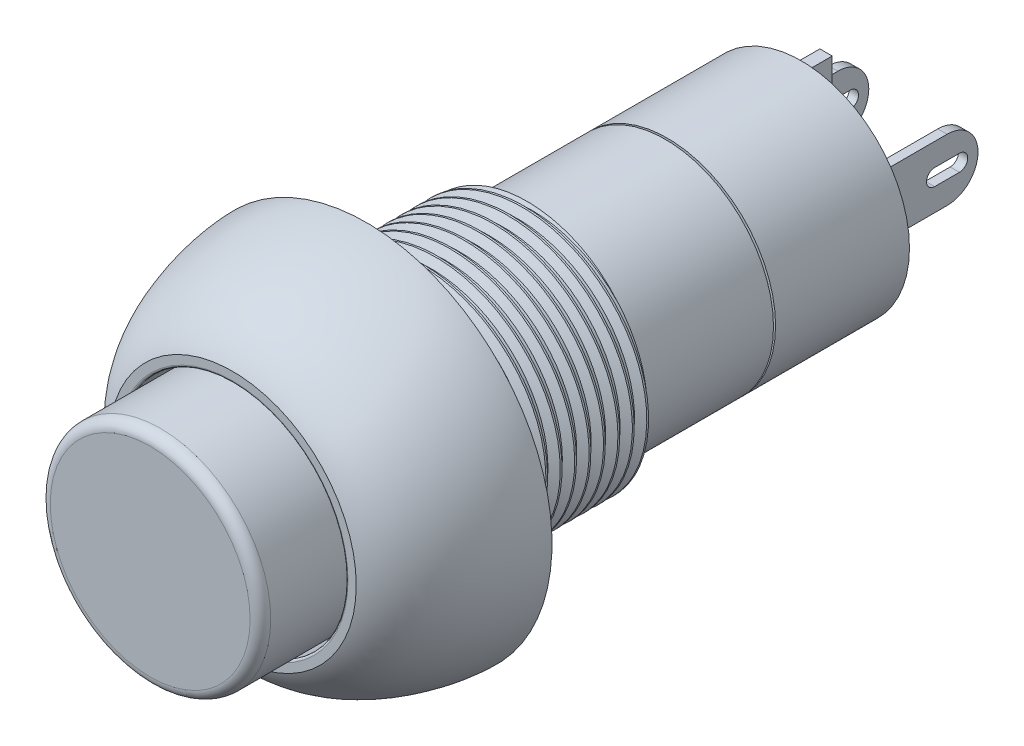
SolidWorks part; units mm, degrees
ref_plane "Спереди" through (0, 0, 0) normal (0, 0, 1) x (1, 0, 0)
ref_plane "Сверху" through (0, 0, 0) normal (0, 1, 0) x (1, 0, 0)
ref_plane "Справа" through (0, 0, 0) normal (1, 0, 0) x (0, 0, -1)
sketch "Эскиз1" plane through (0, 0, 0) normal (0, 0, 1) x (1, 0, 0)
  circle A0 centre (0, 0) radius 6
  dimension "D1" = 12
extrude "Бобышка-Вытянуть1" add sketch "Эскиз1" along normal blind 8
sketch "Эскиз2" plane through (0, 0, 0) normal (0, 0, -1) x (-1, 0, 0)
  circle A0 centre (0, 0) radius 5.25
  dimension "D1" = 10.5
extrude "Бобышка-Вытянуть2" add sketch "Эскиз2" along normal blind 6.5
thread "Резьба1" pitch 0.7 method cut profile "Профиль резьбы1" start angle 0, offset 1, length 10, pitch 0.7, diameter 12
ref_plane "Плоскость4" through (6, 0, -1) normal (0, -1, 0) x (1, 0, 0)
sketch "Профиль резьбы1" plane through (6, 0, -1) normal (0, -1, 0) x (1, 0, 0)
  line L0 (0, 0) -> (0, 0.7) construction
  line L11 (0, 0) -> (0, 0.6125)
  line L12 (0, 0.6125) -> (-0.3789, 0.3937)
  line L13 (-0.3789, 0.3937) -> (-0.3789, 0.2187)
  line L15 (-0.3789, 0.2187) -> (0, 0)
  line L17 (-0.3789, 0.3062) -> (0, 0.3062) construction
  point P2 (0, 0)
  dimension "Pitch" = 0.7
  dimension "Profile_Angle" = 60
  dimension "Profile_Land" = 0.175
  dimension "Profile_Height" = 0.3789
sketch "Эскиз8" plane through (0, 0, -6.5) normal (0, 0, -1) x (-1, 0, 0)
  circle A0 centre (0, 0) radius 5.1
  dimension "D1" = 10.2
extrude "Бобышка-Вытянуть3" add sketch "Эскиз8" along normal blind 0.1
sketch "Эскиз9" plane through (0, 0, -6.6) normal (0, 0, -1) x (-1, 0, 0)
  circle A0 centre (0, 0) radius 5.25 construction
  circle A1 centre (0, 0) radius 5.25
extrude "Бобышка-Вытянуть4" add sketch "Эскиз9" along normal blind 6.5
sketch "Эскиз10" plane through (0, 0, -13.1) normal (0, 0, -1) x (-1, 0, 0)
  circle A0 centre (0, 0) radius 5.25 construction
  circle A1 centre (0, 0) radius 5.25 construction
  circle A2 centre (0, 0) radius 5
  dimension "D1" = 0.25
extrude "Вырез-Вытянуть1" cut sketch "Эскиз10" against normal blind 0.3
sketch "Эскиз11" plane through (0, 0, -12.8) normal (0, 0, -1) x (-1, 0, 0)
  line L0 (0, 5) -> (0, -5) construction
  line L1 (-0.3, 5) -> (-0.3, -5)
  line L2 (0.3, 5) -> (0.3, -5)
  line L3 (-0.3, 5) -> (0.3, 5)
  line L4 (-0.3, -5) -> (0.3, -5)
  circle A0 centre (0, 0) radius 5 construction
  circle A1 centre (0, 0) radius 5 construction
  dimension "D1" = 0.3
  dimension "D2" = 0.3
extrude "Бобышка-Вытянуть5" add sketch "Эскиз11" along normal blind 1.5
sketch "Эскиз12" plane through (0, 0, -12.8) normal (0, 0, -1) x (-1, 0, 0)
  line L0 (-0.3, 0) -> (-5, 0) construction
  line L1 (-0.3, 5) -> (-0.3, -5) construction
  line L2 (-2.9, -2.5) -> (-2.4, -2.5)
  line L3 (-2.9, -2.5) -> (-2.9, -0.433)
  line L4 (-2.4, -2.5) -> (-2.4, -0.433)
  line L5 (-2.9, 2.5) -> (-2.4, 2.5)
  line L6 (0, 5) -> (0, -5) construction
  line L7 (-0.3, 5) -> (0.3, 5) construction
  line L8 (-2.4, 0.433) -> (-2.4, 2.5)
  line L9 (-2.9, 0.433) -> (-2.9, 2.5)
  line L10 (-0.3, -5) -> (0.3, -5) construction
  line L11 (2.9, 0.433) -> (2.9, 2.5)
  line L12 (2.9, -2.5) -> (2.9, -0.433)
  line L13 (2.9, -2.5) -> (2.4, -2.5)
  line L14 (2.4, -2.5) -> (2.4, -0.433)
  line L15 (2.4, 0.433) -> (2.4, 2.5)
  line L16 (2.9, 2.5) -> (2.4, 2.5)
  arc A0 (-0.3, 4.991) -> (-0.3, -4.991) centre (0, 0) ccw construction
  arc A1 (-2.4, -0.433) -> (-2.4, 0.433) centre (-2.65, 0) ccw
  arc A2 (-2.9, 0.433) -> (-2.9, -0.433) centre (-2.65, 0) ccw
  arc A3 (2.9, 0.433) -> (2.9, -0.433) centre (2.65, 0) cw
  arc A4 (2.4, -0.433) -> (2.4, 0.433) centre (2.65, 0) cw
  dimension "D1" = 1
  dimension "D2" = 0.5
  dimension "D3" = 5
  dimension "D4" = 0.25
  dimension "D5" = 2.5
extrude "Вырез-Вытянуть2" cut sketch "Эскиз12" against normal blind 4
sketch "Эскиз13" plane through (0, 0, -8.8) normal (0, 0, -1) x (-1, 0, 0)
  line L0 (-3.15, 0) -> (-2.15, 0) construction
  line L1 (-2.875, -2.475) -> (-2.425, -2.475)
  line L2 (-2.875, -2.475) -> (-2.875, 2.475)
  line L3 (-2.425, -2.475) -> (-2.425, 2.475)
  line L4 (-2.875, 2.475) -> (-2.425, 2.475)
  line L5 (-2.875, -2.475) -> (-2.425, 2.475) construction
  line L6 (-2.425, -2.475) -> (-2.875, 2.475) construction
  line L7 (0, 0) -> (0, 5) construction
  line L8 (-0.3, 5) -> (0.3, 5) construction
  line L9 (2.425, -2.475) -> (2.425, 2.475)
  line L10 (2.875, 2.475) -> (2.425, 2.475)
  line L11 (2.875, -2.475) -> (2.875, 2.475)
  line L12 (2.875, -2.475) -> (2.425, -2.475)
  arc A0 (-2.9, 0.433) -> (-2.9, -0.433) centre (-2.65, 0) ccw construction
  arc A1 (-2.4, -0.433) -> (-2.4, 0.433) centre (-2.65, 0) ccw construction
  point P9 (-2.65, 0)
  dimension "D1" = 4.95
  dimension "D2" = 0.45
extrude "Бобышка-Вытянуть6" add sketch "Эскиз13" along normal blind 4.5
sketch "Эскиз14" plane through (0, 0, -13.3) normal (0, 0, -1) x (-1, 0, 0)
  line L0 (-2.65, 2.475) -> (-2.65, -2.475) construction
  line L1 (-2.425, 2.475) -> (-2.875, 2.475) construction
  line L2 (-2.875, -2.475) -> (-2.425, -2.475) construction
  line L3 (-2.875, -1.5) -> (-2.425, -1.5)
  line L4 (-2.875, -1.5) -> (-2.875, 1.5)
  line L5 (-2.425, -1.5) -> (-2.425, 1.5)
  line L6 (-2.875, 1.5) -> (-2.425, 1.5)
  line L7 (-2.875, -1.5) -> (-2.425, 1.5) construction
  line L8 (-2.425, -1.5) -> (-2.875, 1.5) construction
  line L9 (-2.875, 2.475) -> (-2.875, -2.475) construction
  line L10 (0, 0) -> (0, 5) construction
  line L11 (-0.3, 5) -> (0.3, 5) construction
  line L12 (2.425, -1.5) -> (2.425, 1.5)
  line L13 (2.875, 1.5) -> (2.425, 1.5)
  line L14 (2.875, -1.5) -> (2.875, 1.5)
  line L15 (2.875, -1.5) -> (2.425, -1.5)
  point P7 (-2.65, 0)
  dimension "D1" = 3
extrude "Бобышка-Вытянуть7" add sketch "Эскиз14" along normal blind 5.5
sketch "Эскиз15" plane through (2.875, 0, 0) normal (1, 0, 0) x (0, 0, -1)
  line L0 (18.8, 0) -> (13.1, 0) construction
  line L1 (18.8, 1.5) -> (18.8, -1.5) construction
  line L2 (13.1, -5.25) -> (13.1, 5.25) construction
  line L3 (18.8, 1.5) -> (13.3, 1.5) construction
  line L4 (16.7, 0) -> (17.9, 0) construction
  line L7 (17.3, 1.5) -> (17.3, 1.8711)
  line L8 (17.3, 1.8711) -> (19.8995, 1.8711)
  line L9 (19.8995, 1.8711) -> (19.8995, -2.2852)
  line L10 (19.8995, -2.2852) -> (17.3, -2.2852)
  line L11 (17.3, -2.2852) -> (17.3, -1.5)
  line L12 (18.8, -1.5) -> (13.3, -1.5) construction
  line L13 (16.7, 0.4) -> (17.9, 0.4)
  line L14 (16.7, -0.4) -> (17.9, -0.4)
  arc A0 (17.3, -1.5) -> (17.3, 1.5) centre (17.3, 0) ccw
  arc A3 (16.7, 0.4) -> (16.7, -0.4) centre (16.7, 0) ccw
  arc A4 (17.9, -0.4) -> (17.9, 0.4) centre (17.9, 0) ccw
  point P7 (17.3, 0)
  dimension "D1" = 0.8
  dimension "D2" = 1.2
  dimension "D3" = 4.1563
  dimension "D4" = 2.5995
  dimension "D5" = 0.7852
  dimension "D6" = 0.3711
extrude "Вырез-Вытянуть3" cut sketch "Эскиз15" against normal blind 7.5
sketch "Эскиз16" plane through (0, 0, 0) normal (1, 0, 0) x (0, 0, -1)
  line L0 (0, 0) -> (-8, 0) construction
  line L1 (-8, 5.6788) -> (-8, -0.7175) construction
  line L2 (-8, 0) -> (-14.5, 0)
  line L3 (-14.5, 0) -> (-14.5, 6)
  line L4 (-8, 0) -> (-8, 9)
  spline S0 degree 3 poles (-14.5, 6) (-13.4789, 8.0977) (-9.8641, 9) (-8, 9) knots 0 0 0 0 1 1 1 1
  dimension "D1" = 6.5
  dimension "D2" = 6
  dimension "D3" = 9
revolve "Повернуть1" add sketch "Эскиз16" angle 360 about L0
sketch "Эскиз17" plane through (0, 0, 14.5) normal (0, 0, 1) x (1, 0, 0)
  circle A2 centre (0, 0) radius 5.5
  circle A3 centre (0, 0) radius 5.5
  dimension "D1" = 0.5
extrude "Вырез-Вытянуть4" cut sketch "Эскиз17" against normal blind 5.5
sketch "Эскиз19" plane through (0, 0, 9) normal (0, 0, 1) x (1, 0, 0)
  circle A2 centre (0, 0) radius 5.35
  circle A3 centre (0, 0) radius 5.35
  dimension "D1" = 0.15
extrude "Бобышка-Вытянуть8" add sketch "Эскиз19" along normal blind 9.5
fillet "Скругление1" radius 0.5 1 edges at (5.35, 0, 18.5)
fillet "Скругление2" radius 0.1 1 edges at (5.5, 0, 14.5)
